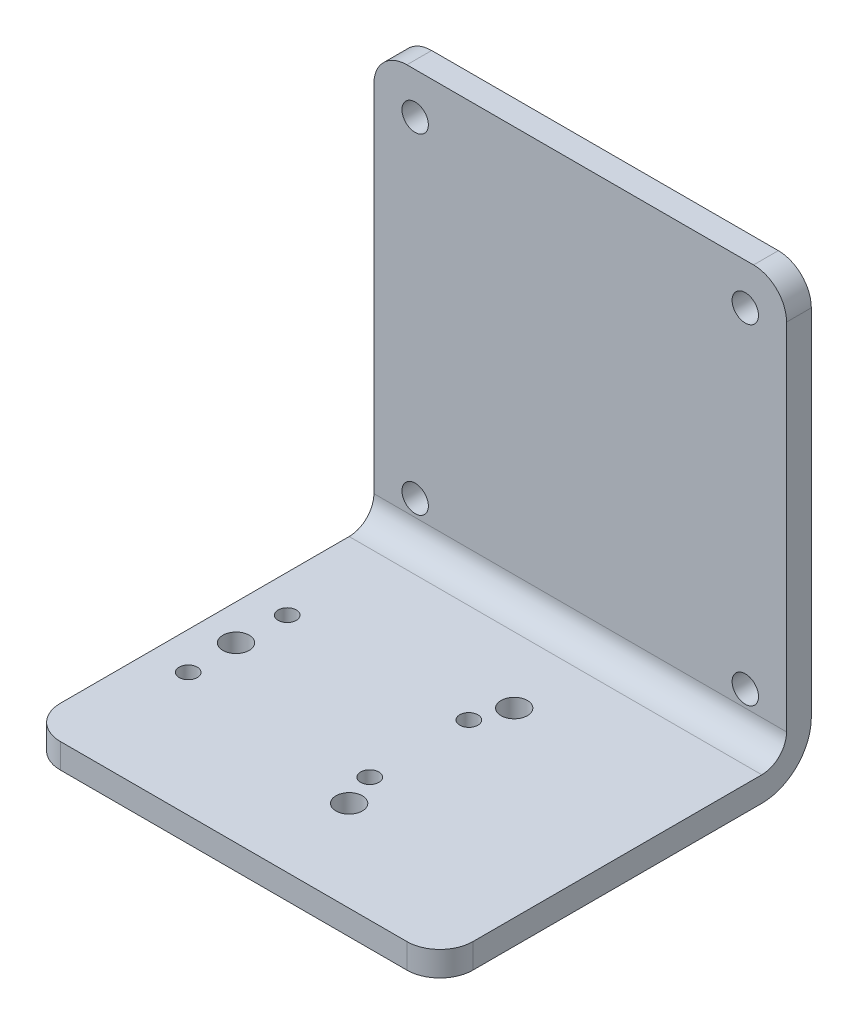
SolidWorks part; units mm, degrees
ref_plane "Front Plane" through (0, 0, 0) normal (0, 0, 1) x (1, 0, 0)
ref_plane "Top Plane" through (0, 0, 0) normal (0, 1, 0) x (1, 0, 0)
ref_plane "Right Plane" through (0, 0, 0) normal (1, 0, 0) x (0, 0, -1)
sketch "Sketch1" plane through (0, 0, 0) normal (0, 1, 0) x (1, 0, 0)
  line L1 (-25, -22.5) -> (25, -22.5)
  line L2 (-25, -22.5) -> (-25, 22.5)
  line L3 (-25, 22.5) -> (25, 22.5)
  line L4 (25, -22.5) -> (25, 22.5)
  line L5 (-25, -22.5) -> (25, 22.5) construction
  line L6 (-25, 22.5) -> (25, -22.5) construction
  point P0 (0, 0)
  dimension "D1" = 50
  dimension "D2" = 45
extrude "Boss-Extrude1" add sketch "Sketch1" along normal blind 3
sketch "Sketch2" plane through (0, 3, 0) normal (0, 1, 0) x (1, 0, 0)
  line L0 (25, -22.5) -> (25, 22.5) construction
  line L1 (-25, 22.5) -> (25, 22.5)
  line L2 (-25, 22.5) -> (-25, 19.5)
  line L3 (-25, 19.5) -> (25, 19.5)
  line L4 (25, 22.5) -> (25, 19.5)
  dimension "D1" = 3
extrude "Boss-Extrude2" add sketch "Sketch2" along normal blind 50
sketch "Sketch3" plane through (0, 3, 0) normal (0, 1, 0) x (1, 0, 0)
  line L0 (-25, -1.5) -> (25, -1.5) construction
  line L3 (-25, 19.5) -> (-25, -22.5) construction
  line L4 (25, -22.5) -> (25, 19.5) construction
  line L5 (18, 42.7187) -> (18, -42.7973) construction
  circle A2 centre (3, 8.5) radius 1.6
  circle A3 centre (3, -11.5) radius 1.6
  circle A4 centre (-20.7, -1.5) radius 1.6
  circle A5 centre (1.5, 4.5) radius 1.1
  circle A6 centre (1.5, -7.5) radius 1.1
  circle A7 centre (-20.5, 4.5) radius 1.1
  circle A8 centre (-20.5, -7.5) radius 1.1
  dimension "D2" = 3.2
  dimension "D5" = 3.2
  dimension "D9" = 2.2
  dimension "D3" = 15
  dimension "D4" = 10
  dimension "D6" = 23.7
  dimension "D7" = 16.5
  dimension "D8" = 6
  dimension "D10" = 22
  dimension "D11" = 7
extrude "Cut-Extrude1" cut sketch "Sketch3" against normal up to surface (3 mm away) up to face at (0, 0, 0)
sketch "Sketch4" plane through (0, 0, -19.5) normal (0, 0, 1) x (1, 0, 0)
  line L0 (25, 53) -> (25, 3) construction
  line L1 (-20, 48) -> (20, 48) construction
  line L2 (-20, 48) -> (-20, 8) construction
  line L3 (-20, 8) -> (20, 8) construction
  line L4 (20, 48) -> (20, 8) construction
  line L5 (-25, 53) -> (25, 53) construction
  line L6 (-20, 48) -> (-18.8686, 46.8686) construction
  line L7 (20, 48) -> (18.8686, 46.8686) construction
  line L8 (-18.8686, 9.1314) -> (-20, 8) construction
  line L9 (18.8686, 9.1314) -> (20, 8) construction
  circle A0 centre (-20, 48) radius 1.6
  circle A1 centre (20, 48) radius 1.6
  circle A2 centre (20, 8) radius 1.6
  circle A3 centre (-20, 8) radius 1.6
  point P4 (20, 28)
  point P7 (25, 28)
  point P8 (0, 48)
  point P11 (0, 53)
  dimension "D2" = 3.2
  dimension "D1" = 40
extrude "Cut-Extrude2" cut sketch "Sketch4" against normal up to surface (3 mm away) up to face at (0, 26.5, -22.5)
fillet "Fillet1" radius 4 4 edges at (25, 53, -21) (-25, 53, -21) (25, 1.5, 22.5) (-25, 1.5, 22.5)
fillet "Fillet2" radius 3 1 edges at (0, 3, -19.5)
fillet "Fillet3" radius 6 1 edges at (0, 0, -22.5)
